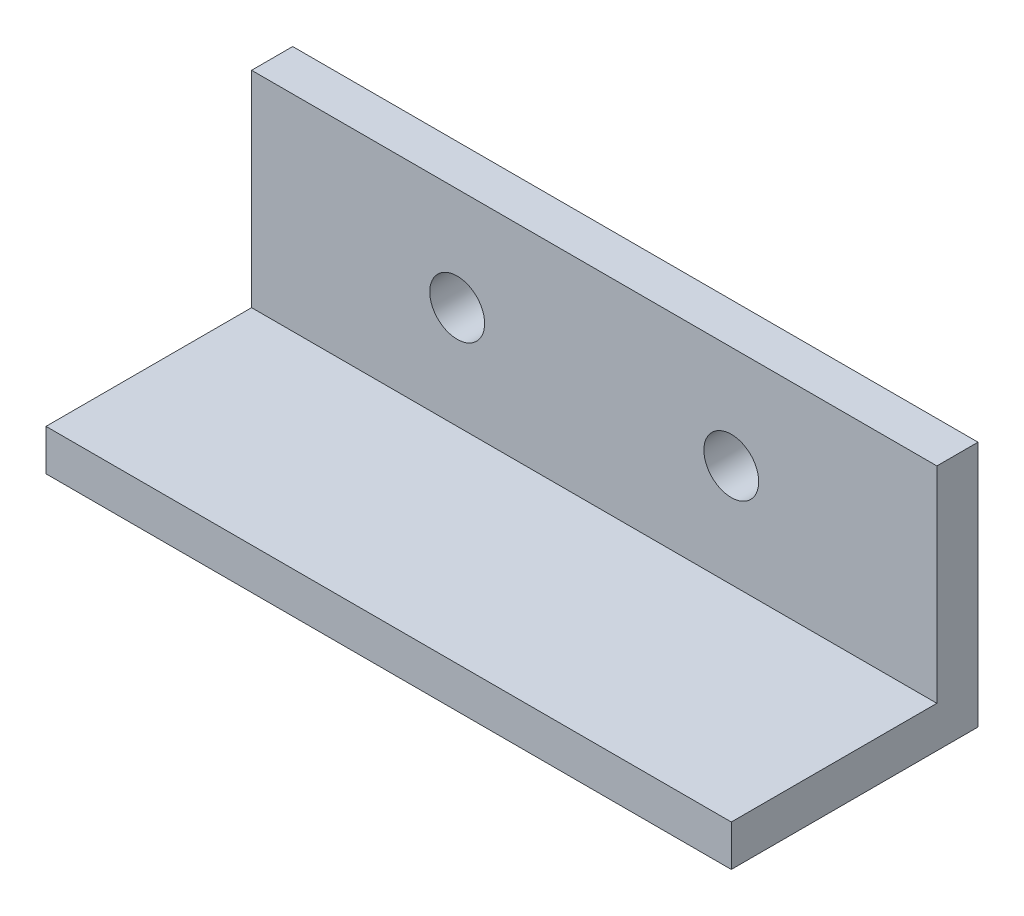
SolidWorks part; units mm, degrees
ref_plane "Front Plane" through (0, 0, 0) normal (0, 0, 1) x (1, 0, 0)
ref_plane "Top Plane" through (0, 0, 0) normal (0, 1, 0) x (1, 0, 0)
ref_plane "Right Plane" through (0, 0, 0) normal (1, 0, 0) x (0, 0, -1)
sketch "Sketch1" plane through (0, 0, 0) normal (0, 1, 0) x (1, 0, 0)
  line L1 (-25, -7.5) -> (25, -7.5)
  line L2 (-25, -7.5) -> (-25, 7.5)
  line L3 (-25, 7.5) -> (25, 7.5)
  line L4 (25, -7.5) -> (25, 7.5)
  line L5 (-25, -7.5) -> (25, 7.5) construction
  line L6 (-25, 7.5) -> (25, -7.5) construction
  point P0 (0, 0)
  dimension "D1" = 50
  dimension "D2" = 15
extrude "Boss-Extrude1" add sketch "Sketch1" along normal blind 3
sketch "Sketch2" plane through (0, 0, 0) normal (0, -1, 0) x (1, 0, 0)
  line L0 (-25, -7.5) -> (-25, 7.5) construction
  line L1 (25, -7.5) -> (-25, -7.5)
  line L2 (25, -7.5) -> (25, -10.5)
  line L3 (25, -10.5) -> (-25, -10.5)
  line L4 (-25, -7.5) -> (-25, -10.5)
  point P4 (0, 0)
  point P5 (0, 0)
  dimension "D1" = 3
extrude "Boss-Extrude2" add sketch "Sketch2" against normal blind 18
sketch "Sketch3" plane through (0, 0, -7.5) normal (0, 0, 1) x (1, 0, 0)
  line L0 (0, 18) -> (0, 3) construction
  line L1 (25, 18) -> (-25, 18) construction
  line L2 (-25, 3) -> (25, 3) construction
  circle A0 centre (-10, 10.5) radius 2
  circle A1 centre (10, 10.5) radius 2
  dimension "D1" = 4
  dimension "D2" = 10
extrude "Cut-Extrude1" cut sketch "Sketch3" against normal blind 3
